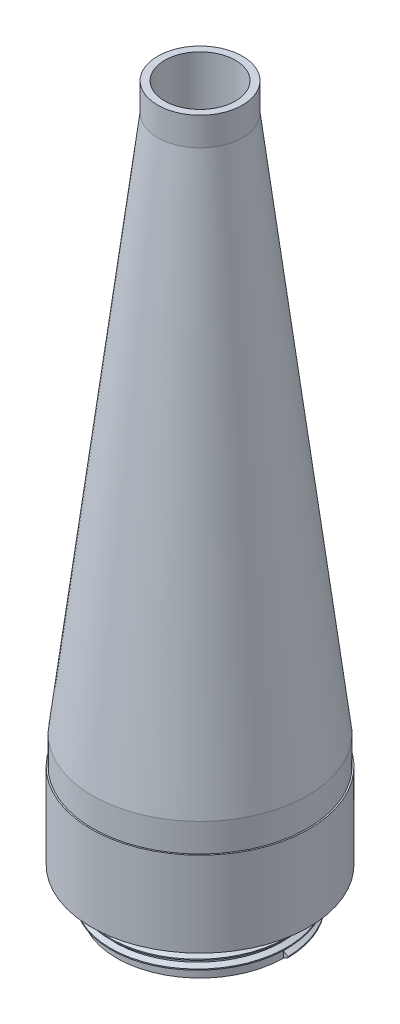
SolidWorks part; units mm, degrees
ref_plane "Alzado" through (0, 0, 0) normal (0, 0, 1) x (1, 0, 0)
ref_plane "Planta" through (0, 0, 0) normal (0, 1, 0) x (1, 0, 0)
ref_plane "Vista lateral" through (0, 0, 0) normal (1, 0, 0) x (0, 0, -1)
sketch "Croquis1" plane through (0, 0, 0) normal (0, 1, 0) x (1, 0, 0)
  circle A0 centre (0, 0) radius 38
  dimension "D1" = 76
extrude "Saliente-Extruir1" add sketch "Croquis1" along normal blind 40 contours A0
ref_plane "Plano1" through (0, 230, 0) normal (0, 1, 0) x (1, 0, 0)
sketch "Croquis2" plane through (0, 230, 0) normal (0, 1, 0) x (1, 0, 0)
  circle A0 centre (0, 0) radius 15
  dimension "D1" = 30
loft "Recubrir1" add profiles "Croquis2" section "Croquis2" section edge at (0, 40, 38)
sketch "Croquis3" plane through (0, 0, 0) normal (0, -1, 0) x (1, 0, 0)
  circle A0 centre (0, 0) radius 20.75
  dimension "D1" = 41.5
extrude "Cortar-Extruir1" cut sketch "Croquis3" against normal blind 113
sketch "Croquis4" plane through (0, 0, 0) normal (0, -1, 0) x (1, 0, 0)
  circle A0 centre (0, 0) radius 22
  dimension "D1" = 44
extrude "Cortar-Extruir2" cut sketch "Croquis4" against normal blind 2
sketch "Croquis5" plane through (0, 230, 0) normal (0, 1, 0) x (1, 0, 0)
  circle A0 centre (0, 0) radius 12.5
  dimension "D1" = 25
extrude "Cortar-Extruir3" cut sketch "Croquis5" against normal blind 119
chamfer "Chaflán1" distance 11 angle 65 1 edges at (0, 113, -12.5) first distance on face at (0, 113, -12.5)
sketch "Croquis6" plane through (0, 0, 0) normal (0, -1, 0) x (1, 0, 0)
  circle A0 centre (0, 0) radius 29.5
  circle A1 centre (0, 0) radius 22 construction
  circle A2 centre (0, 0) radius 22
  dimension "D1" = 59
extrude "Saliente-Extruir2" add sketch "Croquis6" along normal blind 14
thread "Rosca1" pitch 3 method extrude profile "Perfil de rosca1" start angle 0, offset 0, length 0, pitch 3, diameter 59
ref_plane "Plano2" through (29.5, -14, 0) normal (0, 0, 1) x (1, 0, 0)
sketch "Perfil de rosca1" plane through (29.5, -14, 0) normal (0, 0, 1) x (1, 0, 0)
  line L0 (0, 0) -> (0, 3) construction
  line L1 (0, 0) -> (1.6238, 0.9375)
  line L2 (1.6238, 0.9375) -> (1.6238, 1.3125)
  line L3 (1.6238, 1.3125) -> (0, 2.25)
  line L4 (1.6238, 1.125) -> (0, 1.125) construction
  line L11 (0, 0) -> (0, 2.25)
  point P2 (0, 0)
  dimension "Pitch" = 3
  dimension "Profile_Angle" = 60
  dimension "Profile_Land" = 0.375
  dimension "Profile_Height" = 1.6238
sketch "Croquis7" plane through (0, 0, 0) normal (0, -1, 0) x (1, 0, 0)
  circle A0 centre (0, 0) radius 38.5
  circle A1 centre (0, 0) radius 38 construction
  circle A2 centre (0, 0) radius 38
  dimension "D1" = 77
extrude "Saliente-Extruir3" add sketch "Croquis7" against normal blind 30 contours A0
sketch "Croquis8" plane through (0, 230, 0) normal (0, 1, 0) x (1, 0, 0)
  circle A0 centre (0, 0) radius 12.5 construction
  circle A1 centre (0, 0) radius 15
  circle A2 centre (0, 0) radius 15
  circle A3 centre (0, 0) radius 12.5
  dimension "D1" = 0
extrude "Saliente-Extruir4" add sketch "Croquis8" along normal blind 10
